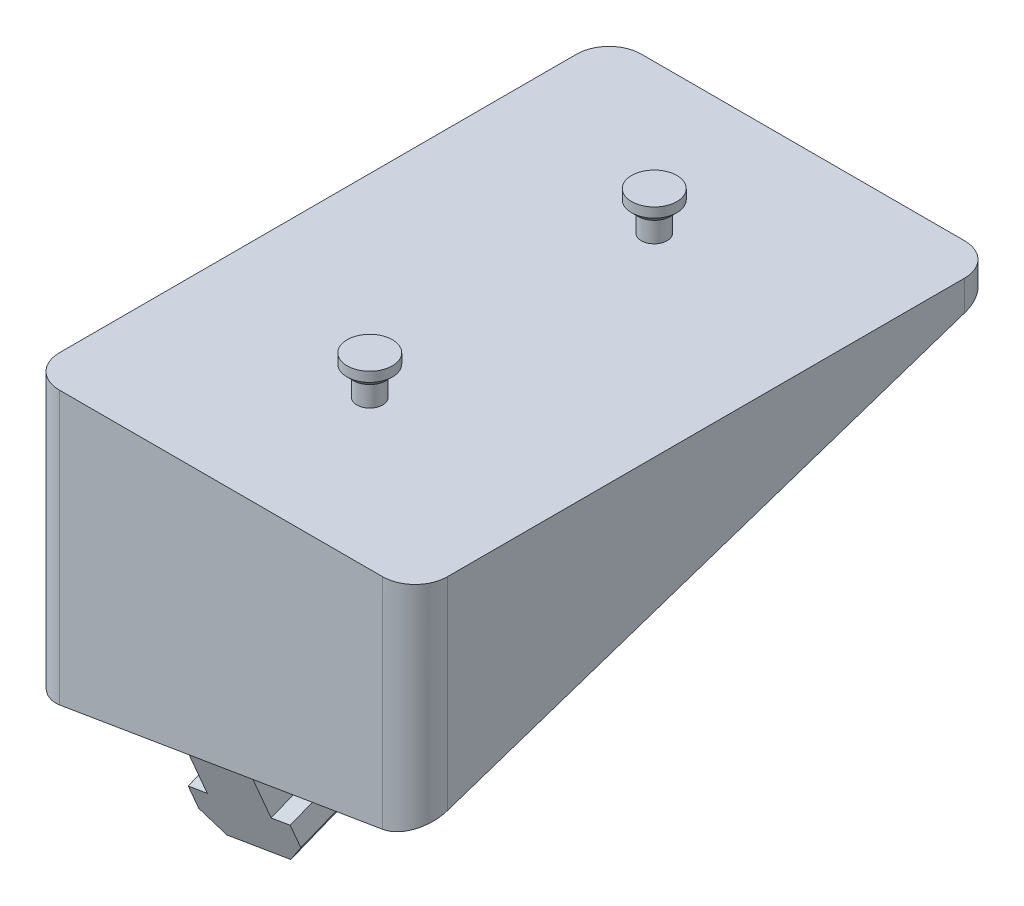
SolidWorks part; units mm, degrees
ref_plane "Front Plane" through (0, 0, 0) normal (0, 0, 1) x (1, 0, 0)
ref_plane "Top Plane" through (0, 0, 0) normal (0, 1, 0) x (1, 0, 0)
ref_plane "Right Plane" through (0, 0, 0) normal (1, 0, 0) x (0, 0, -1)
sketch "Sketch1" plane through (0, 0, 0) normal (0, 1, 0) x (1, 0, 0)
  line L0 (0, 0) -> (60, 0)
  line L1 (60, 0) -> (60, -90)
  line L2 (60, -90) -> (0, -90)
  line L3 (0, -90) -> (0, 0)
  dimension "D1" = 60
  dimension "D2" = 90
extrude "Boss-Extrude1" add sketch "Sketch1" along normal blind 1 and the other way blind 2
sketch "Sketch2" plane through (0, 1, 0) normal (0, 1, 0) x (1, 0, 0)
  line L0 (60, -90) -> (60, 0) construction
  line L1 (60, 0) -> (0, 0) construction
  circle A0 centre (30, -23) radius 2
  circle A1 centre (30, -67) radius 2
  dimension "D3" = 4
  dimension "D4" = 4
  dimension "D1" = 44
  dimension "D2" = 23
  dimension "D5" = 30
  dimension "D6" = 30
extrude "Boss-Extrude2" add sketch "Sketch2" along normal blind 3.5
sketch "Sketch3" plane through (0, 4.5, 0) normal (0, 1, 0) x (1, 0, 0)
  circle A0 centre (30, -23) radius 3.5
  circle A1 centre (30, -67) radius 3.5
  dimension "D1" = 7
  dimension "D2" = 7
extrude "Boss-Extrude3" add sketch "Sketch3" along normal blind 2.5
chamfer "Chamfer1" distance 1 angle 45 2 edges at (30, 4.5, 26.5) (30, 4.5, 70.5)
sketch3d "3DSketch2"
  line L0 (60, -2, 90) -> (60, -32, 90)
  line L1 (0, -2, 90) -> (0, -42, 90)
  dimension "D1" = 40
  dimension "D2" = 30
ref_plane "Plane6" through (1.7561, -10.5366, -3.5122) normal (0.1562, -0.937, -0.3123) x (-0.9877, -0.1482, -0.0494)
extrude "Boss-Extrude5" add sketch "Sketch1<3>" against normal up to surface (42 mm away) up to plane "Plane6"
sketch "Sketch1<3>" plane through (0, 0, 0) normal (0, 1, 0) x (1, 0, 0) same geometry as "Sketch1"
ref_plane "Plane7" through (0, -12, 0) normal (-0.9864, -0.1644, 0) x (0, 0, 1)
ref_plane "Plane8" through (5.0547, -30.3283, 93.5122) normal (-0.0513, 0.3081, -0.95) x (-0.9987, -0.0113, 0.0503)
sketch "Sketch11" plane through (5.0547, -30.3283, 93.5122) normal (-0.0513, 0.3081, -0.95) x (-0.9987, -0.0113, 0.0503)
  line L0 (-25.0133, -7.3109) -> (-27.0268, -19.6477)
  line L1 (5.0034, -12.2099) -> (-55.03, -2.412) construction
  line L2 (-19.1312, -20.9363) -> (-34.9223, -18.3591)
  line L3 (-29.948, -6.5055) -> (-30.9145, -12.4272)
  line L4 (-30.9145, -12.4272) -> (-33.8753, -11.944)
  line L5 (-34.9223, -18.3591) -> (-33.8753, -11.944)
  line L6 (-20.0786, -8.1163) -> (-21.045, -14.038)
  line L7 (-21.045, -14.038) -> (-18.0842, -14.5212)
  line L8 (-19.1312, -20.9363) -> (-18.0842, -14.5212)
  line L9 (-20.0786, -8.1163) -> (-29.948, -6.5055)
  dimension "D1" = 12.5
  dimension "D2" = 8
  dimension "D3" = 6
  dimension "D4" = 5
extrude "Boss-Extrude6" add sketch "Sketch11" along normal up to surface (92.7673 mm away) contours L6 L9 L0 L2 L8 L7 | L0 L9 L3 L4 L5 L2 region at (27.6832, -44.0924, 87.825) region at (34.4918, -42.9576, 87.825) up to face at (30, -3, 0)
chamfer "Chamfer2" distance 3 angle 45 2 edges at (37.5164, -33.4364, 43.0478) (21.7341, -36.0668, 43.0478)
fillet "Fillet1" radius 5 4 edges at (60, -0.5, 0) (0, -5.5, 0) (60, -15.5, 90) (0, -20.5, 90)
